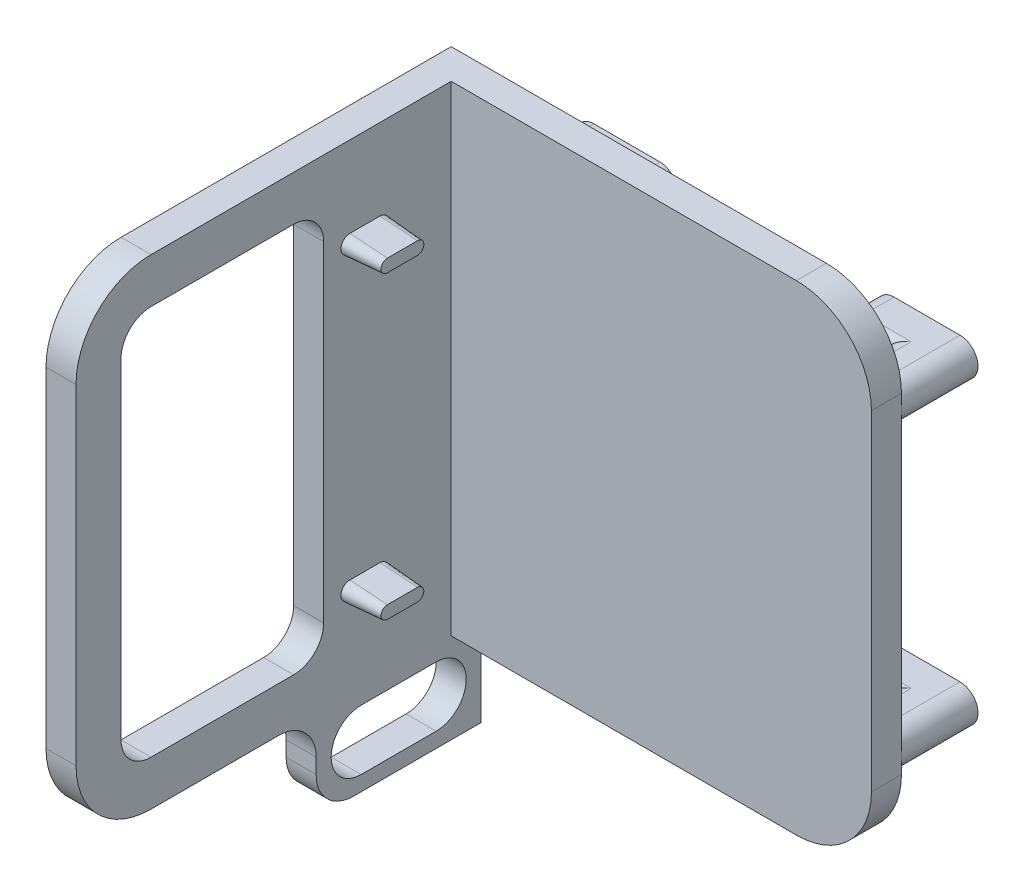
SolidWorks part; units mm, degrees
ref_plane "前视基准面" through (0, 0, 0) normal (0, 0, 1) x (1, 0, 0)
ref_plane "上视基准面" through (0, 0, 0) normal (0, 1, 0) x (1, 0, 0)
ref_plane "右视基准面" through (0, 0, 0) normal (1, 0, 0) x (0, 0, -1)
other "Configuration Table"
sketch "草图1" plane through (0, 0, 0) normal (0, 1, 0) x (1, 0, 0)
  line L1 (-118.5565, 30.4369) -> (-58.5565, 30.4369)
  line L2 (-118.5565, 30.4369) -> (-118.5565, 26.4369)
  line L3 (-118.5565, 26.4369) -> (-58.5565, 26.4369)
  line L4 (-58.5565, 30.4369) -> (-58.5565, 26.4369)
  dimension "D1" = 4
  dimension "D2" = 60
extrude "凸台-拉伸1" add sketch "草图1" along normal blind 64
sketch "草图2" plane through (0, 0, -26.4369) normal (0, 0, 1) x (1, 0, 0)
  line L0 (-118.5565, 0) -> (-58.5565, 0) construction
  line L1 (-118.5565, 64) -> (-114.5565, 64)
  line L2 (-118.5565, 64) -> (-118.5565, 0)
  line L3 (-118.5565, 0) -> (-114.5565, 0)
  line L4 (-114.5565, 64) -> (-114.5565, 0)
  dimension "D1" = 4
extrude "凸台-拉伸2" add sketch "草图2" along normal blind 50
fillet "圆角1" radius 10 4 edges at (-58.5565, 0, -28.4369) (-58.5565, 64, -28.4369) (-116.5565, 0, 23.5631) (-116.5565, 64, 23.5631)
sketch "草图3" plane through (-114.5565, 0, 0) normal (1, 0, 0) x (0, 0, -1)
  line L8 (-17.5631, 54) -> (-17.5631, 10)
  line L9 (-13.5631, 6) -> (20.4369, 6)
  line L10 (20.4369, 6) -> (20.4369, 58)
  line L11 (20.4369, 58) -> (-13.5631, 58)
  line L12 (-17.5631, 54) -> (-17.5631, 10)
  line L13 (-13.5631, 6) -> (20.4369, 6)
  line L14 (20.4369, 6) -> (20.4369, 58)
  line L15 (20.4369, 58) -> (-13.5631, 58)
  arc A4 (-17.5631, 10) -> (-13.5631, 6) centre (-13.5631, 10) ccw
  arc A5 (-13.5631, 58) -> (-17.5631, 54) centre (-13.5631, 54) ccw
  arc A6 (-17.5631, 10) -> (-13.5631, 6) centre (-13.5631, 10) ccw
  arc A7 (-13.5631, 58) -> (-17.5631, 54) centre (-13.5631, 54) ccw
  point P0 (0, 0)
  dimension "D1" = 6
extrude "切除-拉伸1" cut sketch "草图3" against normal up to next
sketch "草图4" plane through (-118.5565, 0, 0) normal (-1, 0, 0) x (0, 0, 1)
  line L0 (-20.4369, 6) -> (13.5631, 6) construction
  line L1 (-20.4369, 58) -> (-9.4369, 58)
  line L2 (-20.4369, 58) -> (-20.4369, 6)
  line L3 (-20.4369, 6) -> (-9.4369, 6)
  line L4 (-9.4369, 58) -> (-9.4369, 6)
  dimension "D1" = 11
extrude "凸台-拉伸3" add sketch "草图4" against normal blind 4 separate body
sketch "草图5" plane through (-114.5565, 0, 0) normal (1, 0, 0) x (0, 0, -1)
  line L0 (12.9369, 52) -> (16.9369, 52) construction
  line L1 (12.9369, 53.2) -> (16.9369, 53.2)
  line L2 (12.9369, 50.8) -> (16.9369, 50.8)
  line L3 (12.9369, 12) -> (16.9369, 12) construction
  line L4 (12.9369, 13.2) -> (16.9369, 13.2)
  line L5 (12.9369, 10.8) -> (16.9369, 10.8)
  arc A0 (12.9369, 53.2) -> (12.9369, 50.8) centre (12.9369, 52) ccw
  arc A1 (16.9369, 50.8) -> (16.9369, 53.2) centre (16.9369, 52) ccw
  arc A2 (12.9369, 13.2) -> (12.9369, 10.8) centre (12.9369, 12) ccw
  arc A3 (16.9369, 10.8) -> (16.9369, 13.2) centre (16.9369, 12) ccw
  point P4 (14.9369, 52)
  point P9 (14.9369, 12)
  dimension "D1" = 1.2
extrude "凸台-拉伸4" add sketch "草图5" along normal blind 5 draft 4
fillet "圆角2" radius 4 2 edges at (-116.5565, 58, -9.4369) (-116.5565, 6, -9.4369)
sketch "草图6" plane through (0, 0, -30.4369) normal (0, 0, -1) x (-1, 0, 0)
  line L0 (60.9565, 52) -> (63.4565, 52) construction
  line L1 (60.9565, 54.4) -> (63.4565, 54.4)
  line L2 (60.9565, 49.6) -> (63.4565, 49.6)
  line L3 (100.9565, 52) -> (103.4565, 52) construction
  line L4 (100.9565, 54.4) -> (103.4565, 54.4)
  line L5 (100.9565, 49.6) -> (103.4565, 49.6)
  line L6 (100.9565, 12) -> (103.4565, 12) construction
  line L7 (100.9565, 14.4) -> (103.4565, 14.4)
  line L8 (100.9565, 9.6) -> (103.4565, 9.6)
  line L9 (60.9565, 12) -> (63.4565, 12) construction
  line L10 (60.9565, 14.4) -> (63.4565, 14.4)
  line L11 (60.9565, 9.6) -> (63.4565, 9.6)
  line L12 (60.9565, 52) -> (60.9565, 12) construction
  line L13 (118.5565, 64) -> (118.5565, 0) construction
  line L14 (58.5565, 54) -> (58.5565, 10) construction
  arc A0 (60.9565, 54.4) -> (60.9565, 49.6) centre (60.9565, 52) ccw
  arc A1 (63.4565, 49.6) -> (63.4565, 54.4) centre (63.4565, 52) ccw
  arc A2 (100.9565, 54.4) -> (100.9565, 49.6) centre (100.9565, 52) ccw
  arc A3 (103.4565, 49.6) -> (103.4565, 54.4) centre (103.4565, 52) ccw
  arc A4 (100.9565, 14.4) -> (100.9565, 9.6) centre (100.9565, 12) ccw
  arc A5 (103.4565, 9.6) -> (103.4565, 14.4) centre (103.4565, 12) ccw
  arc A6 (60.9565, 14.4) -> (60.9565, 9.6) centre (60.9565, 12) ccw
  arc A7 (63.4565, 9.6) -> (63.4565, 14.4) centre (63.4565, 12) ccw
  point P2 (62.2065, 52)
  point P11 (102.2065, 52)
  point P18 (102.2065, 12)
  point P25 (62.2065, 12)
  point P32 (118.5565, 32)
  point P33 (60.9565, 32)
  point P36 (58.5565, 52)
  dimension "D1" = 2.4
  dimension "D2" = 2.5
  dimension "D3" = 2
  dimension "D4" = 2
extrude "凸台-拉伸5" add sketch "草图6" along normal blind 5.2
sketch "草图7" plane through (0, 0, -35.6369) normal (0, 0, -1) x (-1, 0, 0)
  line L0 (60.9565, 52) -> (69.7565, 52) construction
  line L1 (60.9565, 54.4) -> (69.7565, 54.4)
  line L2 (60.9565, 49.6) -> (69.7565, 49.6)
  line L3 (100.9565, 52) -> (109.7565, 52) construction
  line L4 (100.9565, 54.4) -> (109.7565, 54.4)
  line L5 (100.9565, 49.6) -> (109.7565, 49.6)
  line L6 (100.9565, 12) -> (109.7565, 12) construction
  line L7 (100.9565, 14.4) -> (109.7565, 14.4)
  line L8 (100.9565, 9.6) -> (109.7565, 9.6)
  line L9 (60.9565, 12) -> (69.7565, 12) construction
  line L10 (60.9565, 14.4) -> (69.7565, 14.4)
  line L11 (60.9565, 9.6) -> (69.7565, 9.6)
  arc A0 (60.9565, 54.4) -> (60.9565, 49.6) centre (60.9565, 52) ccw
  arc A1 (69.7565, 49.6) -> (69.7565, 54.4) centre (69.7565, 52) ccw
  arc A2 (60.9565, 54.4) -> (60.9565, 49.6) centre (60.9565, 52) ccw construction
  arc A3 (100.9565, 54.4) -> (100.9565, 49.6) centre (100.9565, 52) ccw
  arc A4 (109.7565, 49.6) -> (109.7565, 54.4) centre (109.7565, 52) ccw
  arc A5 (100.9565, 14.4) -> (100.9565, 9.6) centre (100.9565, 12) ccw
  arc A6 (109.7565, 9.6) -> (109.7565, 14.4) centre (109.7565, 12) ccw
  arc A7 (60.9565, 14.4) -> (60.9565, 9.6) centre (60.9565, 12) ccw
  arc A8 (69.7565, 9.6) -> (69.7565, 14.4) centre (69.7565, 12) ccw
  point P3 (65.3565, 52)
  point P15 (105.3565, 52)
  point P22 (105.3565, 12)
  point P29 (65.3565, 12)
  dimension "D1" = 8.8
  dimension "D2" = 2
  dimension "D3" = 2
extrude "凸台-拉伸6" add sketch "草图7" along normal blind 5
fillet "圆角3" radius 1 12 edges at (-66.6065, 49.6, -35.6369) (-66.6065, 54.4, -35.6369) (-66.6065, 9.6, -35.6369) (-66.6065, 14.4, -35.6369) (-106.6065, 9.6, -35.6369) (-106.6065, 14.4, -35.6369) (-106.6065, 49.6, -35.6369) (-106.6065, 54.4, -35.6369) (-72.1565, 52, -35.6369) (-72.1565, 12, -35.6369) (-112.1565, 12, -35.6369) (-112.1565, 52, -35.6369)
sketch "草图8" plane through (0, 0, 0) normal (0, -1, 0) x (1, 0, 0)
  line L0 (-114.5565, 13.5631) -> (-114.5565, -26.4369) construction
  line L1 (-118.5565, -30.4369) -> (-114.5565, -30.4369)
  line L2 (-118.5565, -30.4369) -> (-118.5565, -8.4369)
  line L3 (-118.5565, -8.4369) -> (-114.5565, -8.4369)
  line L4 (-114.5565, -30.4369) -> (-114.5565, -8.4369)
  dimension "D1" = 22
extrude "凸台-拉伸7" add sketch "草图8" along normal blind 12
fillet "圆角4" radius 5 2 edges at (-116.5565, 0, -8.4369) (-116.5565, -12, -8.4369)
sketch "草图9" plane through (-114.5565, 0, 0) normal (1, 0, 0) x (0, 0, -1)
  line L0 (14.4369, -6) -> (24.4369, -6) construction
  line L1 (14.4369, -2) -> (24.4369, -2)
  line L2 (14.4369, -10) -> (24.4369, -10)
  line L3 (30.4369, 0) -> (26.4369, 0) construction
  line L4 (30.4369, -12) -> (30.4369, 0) construction
  arc A0 (14.4369, -2) -> (14.4369, -10) centre (14.4369, -6) ccw
  arc A1 (24.4369, -10) -> (24.4369, -2) centre (24.4369, -6) ccw
  point P2 (19.4369, -6)
  dimension "D2" = 4
  dimension "D1" = 10
  dimension "D3" = 6
  dimension "D4" = 6
extrude "切除-拉伸2" cut sketch "草图9" against normal up to next
